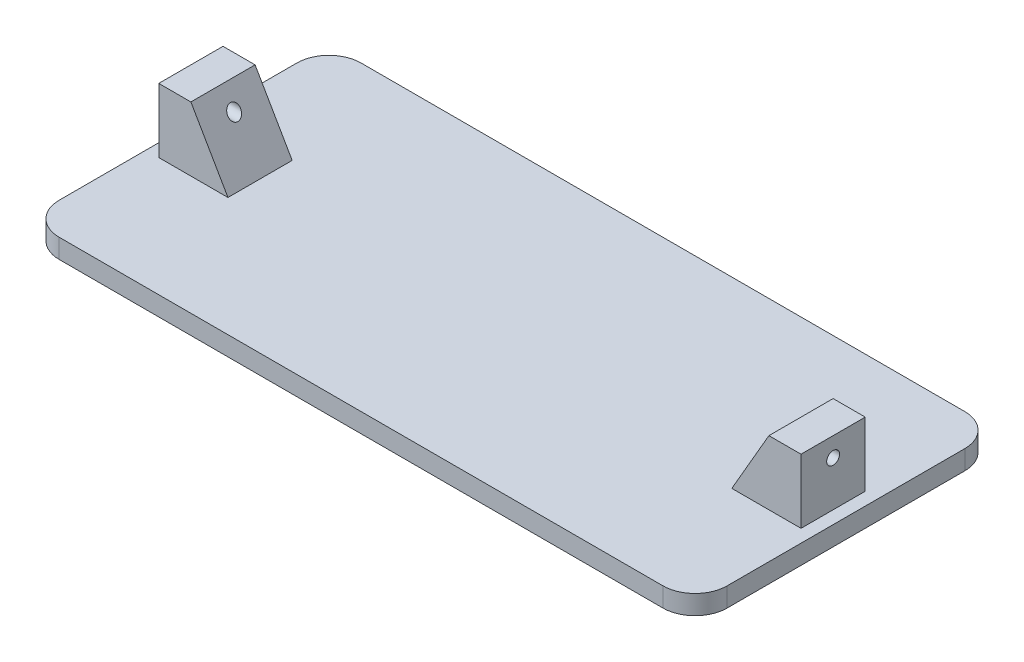
SolidWorks part; units mm, degrees
ref_plane "Спереди" through (0, 0, 0) normal (0, 0, 1) x (1, 0, 0)
ref_plane "Сверху" through (0, 0, 0) normal (0, 1, 0) x (1, 0, 0)
ref_plane "Справа" through (0, 0, 0) normal (1, 0, 0) x (0, 0, -1)
sketch "Эскиз1" plane through (0, 0, 0) normal (0, 1, 0) x (1, 0, 0)
  line L1 (-45, -21.5) -> (45, -21.5)
  line L2 (-50, -16.5) -> (-50, 16.5)
  line L3 (-45, 21.5) -> (45, 21.5)
  line L4 (50, -16.5) -> (50, 16.5)
  line L5 (-50, -21.5) -> (50, 21.5) construction
  line L6 (-50, 21.5) -> (50, -21.5) construction
  arc A0 (50, 16.5) -> (45, 21.5) centre (45, 16.5) ccw
  arc A1 (45, -21.5) -> (50, -16.5) centre (45, -16.5) ccw
  arc A2 (-50, -16.5) -> (-45, -21.5) centre (-45, -16.5) ccw
  arc A3 (-45, 21.5) -> (-50, 16.5) centre (-45, 16.5) ccw
  point P0 (0, 0)
  dimension "D3" = 5
  dimension "D1" = 100
  dimension "D2" = 43
extrude "Бобышка-Вытянуть1" add sketch "Эскиз1" along normal blind 3
sketch "Эскиз3" plane through (0, 0, 0) normal (0, 0, 1) x (1, 0, 0)
  line L0 (-45, 3) -> (-50, 3) construction
  line L1 (-45, 3) -> (-50, 3)
  line L2 (50, 3) -> (45, 3) construction
  line L3 (50, 3) -> (45, 3)
  line L4 (-50, 3) -> (-50, 13)
  line L5 (-50, 13) -> (-45, 13)
  line L6 (-45, 13) -> (-39.2265, 3)
  line L7 (-39.2265, 3) -> (-45, 3)
  line L8 (0, 13.7665) -> (0, -12.3638) construction
  line L9 (39.2265, 3) -> (45, 3)
  line L10 (45, 13) -> (39.2265, 3)
  line L11 (50, 13) -> (45, 13)
  line L12 (50, 3) -> (50, 13)
  line L13 (45, 3) -> (50, 3)
  dimension "D1" = 10
  dimension "D2" = 5
  dimension "D3" = 60
extrude "Бобышка-Вытянуть2" add sketch "Эскиз3" along normal mid plane 10 contours L7 L6 L5 L4 L1 | L3 L12 L11 L10 L9 region at (-45.8805, 7.39, 0) region at (45.8805, 7.39, 0)
sketch "Эскиз4" plane through (-50, 0, 0) normal (-1, 0, 0) x (0, 0, 1)
  line L0 (5, 3) -> (16.5, 3) construction
  line L1 (5, 3) -> (16.5, 3)
  line L2 (0, 0) -> (0, 13) construction
  line L3 (-16.5, 0) -> (16.5, 0) construction
  line L4 (5, 13) -> (-5, 13) construction
  line L5 (-5, 3) -> (-5, 13) construction
  line L6 (-5, 3) -> (-5, 13)
  circle A0 centre (0, 10) radius 1
  dimension "D1" = 2
  dimension "D2" = 10
extrude "Вырез-Вытянуть1" cut sketch "Эскиз4" against normal through all contours A0 | A0 L2 region at (-50, 10, -0.4244) region at (-50, 10, 0.4244)
sketch "Эскиз5" plane through (0, 0, 0) normal (0, -1, 0) x (1, 0, 0)
  line L0 (52, -16.5) -> (52, 16.5)
  line L1 (45, 23.5) -> (-45, 23.5)
  line L2 (-52, 16.5) -> (-52, -16.5)
  line L3 (-45, -23.5) -> (45, -23.5)
  line L4 (50, -16.5) -> (50, 16.5)
  line L5 (45, 21.5) -> (-45, 21.5)
  line L6 (-50, 16.5) -> (-50, -16.5)
  line L7 (-45, -21.5) -> (45, -21.5)
  line L8 (50, -16.5) -> (50, 16.5)
  line L9 (45, 21.5) -> (-45, 21.5)
  line L10 (-50, 16.5) -> (-50, -16.5)
  line L11 (-45, -21.5) -> (45, -21.5)
  line L12 (-52, -16.5) -> (-52, -18.5)
  line L13 (-47, -23.5) -> (-45, -23.5)
  line L14 (45, -23.5) -> (47, -23.5)
  line L15 (52, -18.5) -> (52, -16.5)
  line L16 (45, 23.5) -> (47, 23.5)
  line L17 (52, 18.5) -> (52, 16.5)
  line L18 (-45, 23.5) -> (-47, 23.5)
  line L19 (-52, 18.5) -> (-52, 16.5)
  arc A0 (52, -18.5) -> (47, -23.5) centre (47, -18.5) cw
  arc A1 (52, 18.5) -> (47, 23.5) centre (47, 18.5) ccw
  arc A2 (-47, 23.5) -> (-52, 18.5) centre (-47, 18.5) ccw
  arc A3 (-52, -18.5) -> (-47, -23.5) centre (-47, -18.5) ccw
  arc A4 (45, -21.5) -> (50, -16.5) centre (45, -16.5) ccw
  arc A5 (50, 16.5) -> (45, 21.5) centre (45, 16.5) ccw
  arc A6 (-45, 21.5) -> (-50, 16.5) centre (-45, 16.5) ccw
  arc A7 (-50, -16.5) -> (-45, -21.5) centre (-45, -16.5) ccw
  arc A8 (45, -21.5) -> (50, -16.5) centre (45, -16.5) ccw
  arc A9 (50, 16.5) -> (45, 21.5) centre (45, 16.5) ccw
  arc A10 (-45, 21.5) -> (-50, 16.5) centre (-45, 16.5) ccw
  arc A11 (-50, -16.5) -> (-45, -21.5) centre (-45, -16.5) ccw
  arc A16 (-45, 23.5) -> (-52, 16.5) centre (-45, 16.5) ccw construction
  arc A17 (-52, -16.5) -> (-45, -23.5) centre (-45, -16.5) ccw construction
  arc A18 (45, -23.5) -> (52, -16.5) centre (45, -16.5) ccw construction
  arc A19 (52, 16.5) -> (45, 23.5) centre (45, 16.5) ccw construction
  arc M9 (45, -21.5) -> (50, -16.5) centre (45, -16.5) ccw
  line M10 (50, -16.5) -> (50, 16.5)
  arc M11 (50, 16.5) -> (45, 21.5) centre (45, 16.5) ccw
  line M12 (45, 21.5) -> (-45, 21.5)
  arc M13 (-45, 21.5) -> (-50, 16.5) centre (-45, 16.5) ccw
  line M14 (-50, 16.5) -> (-50, -16.5)
  arc M15 (-50, -16.5) -> (-45, -21.5) centre (-45, -16.5) ccw
  line M16 (-45, -21.5) -> (45, -21.5)
  dimension "D3" = 5
  dimension "D1" = 0
  dimension "D2" = 2
extrude "Бобышка-Вытянуть3" add sketch "Эскиз5" against normal blind 3 contours L3 L0 L1 L2 M9 M16 M15 M14 M13 M12 M11 M10 region at (50.8587, 0, -17.5)
